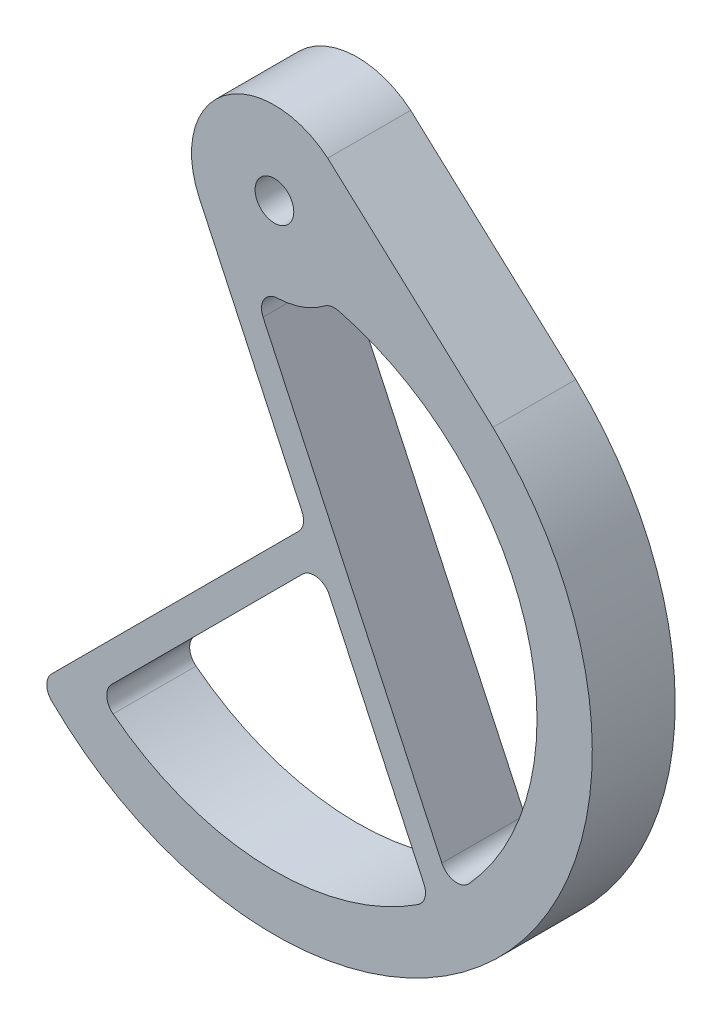
SolidWorks part; units mm, degrees
material "ABS"
ref_plane "正面" through (0, 0, 0) normal (0, 0, 1) x (1, 0, 0)
ref_plane "平面" through (0, 0, 0) normal (0, 1, 0) x (1, 0, 0)
ref_plane "右側面" through (0, 0, 0) normal (1, 0, 0) x (0, 0, -1)
sketch "ｽｹｯﾁ1" plane through (0, 0, 0) normal (0, 0, 1) x (1, 0, 0)
  line L1 (9.9336, 0.7043) -> (27.0462, -35.9938)
  line L2 (9.6418, 68.9907) -> (39.5241, 41.7624)
  line L4 (4.3888, 7.9244) -> (-40.3035, -36.7679)
  line L5 (5.0933, 1.5578) -> (-29.4572, -32.9928)
  line L6 (-13.5946, 51.1607) -> (4.9864, 11.3135)
  line L7 (30.2877, -31.1143) -> (-2.0547, 38.2444)
  arc A0 (-40.2839, -41.0299) -> (37.9168, 43.2269) centre (0, 0) ccw
  arc A1 (-29.1788, -37.4813) -> (25.9673, -39.7737) centre (0, 0) ccw
  arc A2 (0.5535, 42.5102) -> (9.0577, 45.5435) centre (0, 57.5) ccw
  arc A3 (35.2318, -31.8586) -> (11.602, 46.0613) centre (0, 0) ccw
  arc A4 (10.5469, 68.1659) -> (-13.5946, 51.1607) centre (0, 57.5) ccw
  arc A5 (-40.3035, -36.7679) -> (-40.2839, -41.0299) centre (-38.1821, -38.8893) ccw
  arc A6 (-29.4572, -32.9928) -> (-29.1788, -37.4813) centre (-27.3359, -35.1141) ccw
  arc A7 (27.0462, -35.9938) -> (25.9673, -39.7737) centre (24.3273, -37.2617) cw
  arc A8 (5.0933, 1.5578) -> (9.9336, 0.7043) centre (7.2147, -0.5635) cw
  arc A9 (35.2318, -31.8586) -> (30.2877, -31.1143) centre (33.0067, -29.8464) cw
  arc A10 (4.9864, 11.3135) -> (4.3888, 7.9244) centre (2.2675, 10.0457) cw
  arc A11 (-2.0547, 38.2444) -> (0.5535, 42.5102) centre (0.6642, 39.5123) cw
  arc A12 (11.602, 46.0613) -> (9.0577, 45.5435) centre (10.8692, 43.1522) ccw
  point P24 (8.1229, 4.5874)
  dimension "D1" = 3
  dimension "D2" = 3
  dimension "D3" = 3
  dimension "D4" = 3
  dimension "D5" = 3
  dimension "D6" = 3
  dimension "D7" = 3
  dimension "D8" = 3
extrude "ﾎﾞｽ - 押し出し1" add sketch "ｽｹｯﾁ1" along normal blind 15 contours L6 A10 L4 A5 A0 L2 A4 A12 A3 A9 L7 A11 A2 L5 A8 L1 A7 A1 A6 region at (8.9951, 67.3719, 0)
sketch "ｽｹｯﾁ6" plane through (0, 0, 15) normal (0, 0, 1) x (1, 0, 0)
  circle A0 centre (0, 57.5) radius 3.5
extrude "ｶｯﾄ - 押し出し2" cut sketch "ｽｹｯﾁ6" against normal blind 15
sketch "ｽｹｯﾁ8" plane through (0, 0, 0) normal (0, 0, -1) x (-1, 0, 0)
  circle A0 centre (0, 57.5) radius 10.1
extrude "ｶｯﾄ - 押し出し4" cut sketch "ｽｹｯﾁ8" against normal blind 2
sketch "ｽｹｯﾁ9" plane through (0, 0, 2) normal (0, 0, -1) x (-1, 0, 0)
  line L0 (0, 65.5) -> (-3.5, 65.5) construction
  line L1 (0, 57.5) -> (0, 65.5) construction
  line L2 (0, 65.5) -> (3.5, 65.5) construction
  circle A0 centre (-3.5, 65.5) radius 0.5
  circle A1 centre (0, 65.5) radius 0.5
  circle A2 centre (3.5, 65.5) radius 0.5
  circle A3 centre (8, 57.5) radius 0.5
  circle A4 centre (8, 61) radius 0.5
  circle A5 centre (8, 54) radius 0.5
  circle A6 centre (0, 49.5) radius 0.5
  circle A7 centre (3.5, 49.5) radius 0.5
  circle A8 centre (-3.5, 49.5) radius 0.5
  circle A9 centre (-8, 57.5) radius 0.5
  circle A10 centre (-8, 54) radius 0.5
  circle A11 centre (-8, 61) radius 0.5
  point P25 (0, 57.5)
extrude "ｶｯﾄ - 押し出し5" cut sketch "ｽｹｯﾁ9" against normal blind 3
